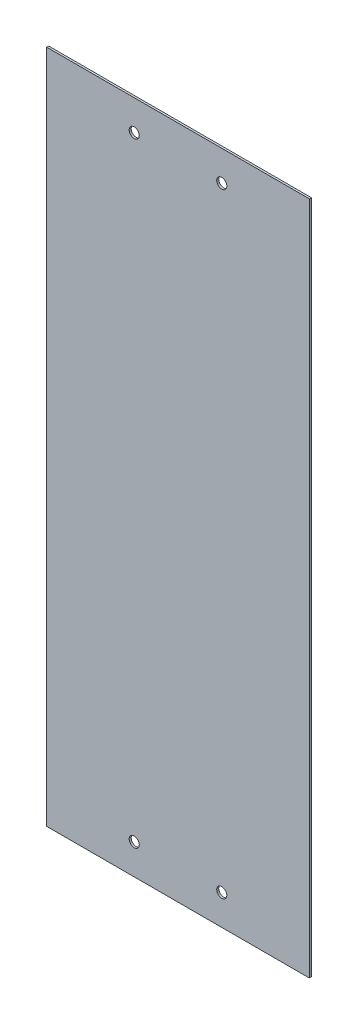
SolidWorks part; units mm, degrees
material "3.0526 (EN-AW 3005)"
ref_plane "Alzado" through (0, 0, 0) normal (0, 0, 1) x (1, 0, 0)
ref_plane "Planta" through (0, 0, 0) normal (0, 1, 0) x (1, 0, 0)
ref_plane "Vista lateral" through (0, 0, 0) normal (1, 0, 0) x (0, 0, -1)
sketch "Croquis1" plane through (0, 0, 0) normal (0, 0, 1) x (1, 0, 0)
  line L0 (-65, 167) -> (-65, 152)
  line L1 (65, -167) -> (-65, -167)
  line L2 (65, -167) -> (65, 167)
  line L3 (65, 167) -> (-65, 167)
  line L4 (-65, -167) -> (-65, 167)
  line L5 (65, -167) -> (-65, 167) construction
  line L6 (65, 167) -> (-65, -167) construction
  line L7 (-65, 152) -> (-21.6667, 152) construction
  line L8 (-21.6667, 152) -> (21.6667, 152) construction
  line L9 (0, 0) -> (85.9766, 0) construction
  circle A0 centre (-21.6667, 152) radius 2.5
  circle A1 centre (21.6667, 152) radius 2.5
  circle A2 centre (21.6667, -152) radius 2.5
  circle A3 centre (-21.6667, -152) radius 2.5
  point P0 (0, 0)
  dimension "D6" = 5
  dimension "D7" = 5
  dimension "D1" = 130
  dimension "D2" = 334
  dimension "D3" = 15
  dimension "D4" = 43.3333
  dimension "D5" = 43.3333
extrude "Saliente-Extruir1" add sketch "Croquis1" along normal blind 1 contours L4 L1 L2 L3 L0 A2 A1 A0 A3 region at (0, 0, 0)
